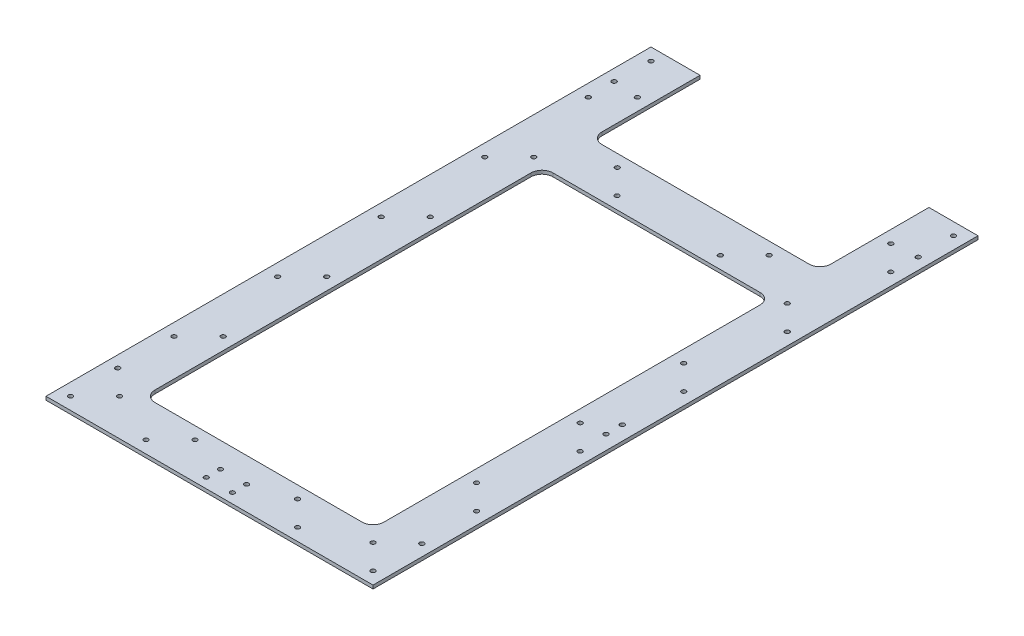
SolidWorks part; units mm, degrees
ref_plane "Front Plane" through (0, 0, 0) normal (0, 0, 1) x (1, 0, 0)
ref_plane "Top Plane" through (0, 0, 0) normal (0, 1, 0) x (1, 0, 0)
ref_plane "Right Plane" through (0, 0, 0) normal (1, 0, 0) x (0, 0, -1)
sketch "Sketch1" plane through (0, 0, 0) normal (0, 1, 0) x (1, 0, 0)
  line L1 (150, -300) -> (-150, -300)
  line L2 (150, -300) -> (150, 300)
  line L3 (150, 300) -> (-150, 300)
  line L4 (-150, -300) -> (-150, 300)
  line L5 (150, -300) -> (-150, 300) construction
  line L6 (150, 300) -> (-150, -300) construction
  point P0 (0, 0)
  dimension "D1" = 600
  dimension "D2" = 300
extrude "Boss-Extrude1" add sketch "Sketch1" along normal blind 3.175
sketch "Sketch3" plane through (0, 3.175, 0) normal (0, 1, 0) x (1, 0, 0)
  line L0 (-95, -255) -> (95, -255)
  line L1 (0, 255) -> (0, -300) construction
  line L2 (105, -245) -> (105, 100)
  line L3 (95, 110) -> (-95, 110)
  line L4 (105, 255) -> (105, 165)
  line L5 (150, 300) -> (-150, 300) construction
  line L6 (95, 155) -> (-95, 155)
  line L8 (0, -300) -> (0, -342.0806) construction
  line L9 (-105, 255) -> (-105, 165)
  line L10 (-105, -245) -> (-105, 100)
  line L11 (50.6601, -255) -> (50.6601, -300) construction
  line L12 (-150, -300) -> (150, -300) construction
  line L13 (105, 27.7939) -> (150, 27.7939) construction
  line L14 (150, -300) -> (150, 300) construction
  line L15 (-150, 27.7939) -> (-105, 27.7939) construction
  line L16 (-150, 300) -> (-150, -300) construction
  line L17 (54.6047, 155) -> (54.6047, 110) construction
  line L18 (105, 255) -> (150, 255)
  line L19 (150, 255) -> (150, 300)
  line L20 (150, 300) -> (-150, 300)
  line L21 (-150, 300) -> (-150, 255)
  line L22 (-150, 255) -> (-105, 255)
  arc A1 (-105, 165) -> (-95, 155) centre (-95, 165) ccw
  arc A3 (105, 165) -> (95, 155) centre (95, 165) cw
  arc A4 (105, 100) -> (95, 110) centre (95, 100) ccw
  arc A5 (-105, 100) -> (-95, 110) centre (-95, 100) cw
  arc A6 (-105, -245) -> (-95, -255) centre (-95, -245) ccw
  arc A7 (95, -255) -> (105, -245) centre (95, -245) ccw
  point P17 (0, 300)
  point P18 (0, 155)
  point P19 (0, 110)
  point P20 (0, -255)
  point P22 (-105.4457, 300)
  point P25 (-105, 155)
  point P28 (105.4457, 300)
  point P31 (105, 155)
  point P34 (105, 110)
  point P37 (-105, 110)
  point P40 (-105, -255)
  point P43 (105, -255)
  dimension "D1" = 45
  dimension "D4" = 10
  dimension "D2" = 45
  dimension "D3" = 145
extrude "Cut-Extrude1" cut sketch "Sketch3" against normal blind 10
sketch "Sketch4" plane through (0, 3.175, 0) normal (0, 1, 0) x (1, 0, 0)
  line L0 (-150, -300) -> (150, -300) construction
  circle A0 centre (12, -291) radius 2.05
  circle A1 centre (-12, -291) radius 2.05
  circle A2 centre (-12, -278) radius 2.05
  circle A3 centre (12, -278) radius 2.05
  point P2 (-27.0179, -300)
  point P16 (-27, -300)
  dimension "D1" = 4.1
  dimension "D2" = 15
  dimension "D3" = 39
  dimension "D4" = 9
  dimension "D5" = 22
extrude "Cut-Extrude2" cut sketch "Sketch4" against normal blind 51
sketch "Sketch5" plane through (0, 3.175, 0) normal (0, 1, 0) x (1, 0, 0)
  circle A0 centre (137, -73.2648) radius 2.1
  circle A1 centre (137, -58.2648) radius 2.1
  circle A2 centre (132, -58.2648) radius 2.15 construction
  point P6 (0, 0)
  point P7 (0, 0)
  point P8 (137.7511, -58.2648)
  point P9 (137.7511, -73.2648)
  point P10 (0, 0)
  dimension "D1" = 4.2
  dimension "D2" = 5
extrude "Cut-Extrude3" cut sketch "Sketch5" against normal blind 67
sketch "Sketch7" plane through (0, 3.175, 0) normal (0, 1, 0) x (1, 0, 0)
  line L0 (138.75, -300) -> (138.75, 255) construction
  line L1 (116.25, -300) -> (116.25, 255) construction
  line L2 (150, -187.519) -> (138.75, -187.519) construction
  line L3 (150, -300) -> (150, 255) construction
  line L4 (138.75, -187.519) -> (127.5, -187.519) construction
  line L5 (127.5, -187.519) -> (116.25, -187.519) construction
  line L6 (116.25, -187.519) -> (105, -187.519) construction
  line L7 (105, -245) -> (105, 100) construction
  line L8 (-150, -300) -> (150, -300) construction
  line L10 (150, 121.25) -> (0, 121.25) construction
  line L11 (105, 255) -> (150, 255) construction
  line L12 (150, 143.75) -> (0, 143.75) construction
  line L13 (33.148, 155) -> (33.148, 143.75) construction
  line L14 (-95, 155) -> (95, 155) construction
  line L15 (33.148, 143.75) -> (33.148, 132.5) construction
  line L16 (33.148, 132.5) -> (33.148, 121.25) construction
  line L17 (33.148, 121.25) -> (33.148, 110) construction
  line L18 (95, 110) -> (-95, 110) construction
  line L19 (150, -288.75) -> (0, -288.75) construction
  line L20 (150, -266.25) -> (0, -266.25) construction
  line L21 (55.7313, -255) -> (55.7313, -266.25) construction
  line L22 (-95, -255) -> (95, -255) construction
  line L23 (55.7313, -266.25) -> (55.7313, -277.5) construction
  line L24 (55.7313, -277.5) -> (55.7313, -288.75) construction
  line L25 (55.7313, -288.75) -> (55.7313, -300) construction
  line L26 (-42.5408, 110) -> (-42.5408, -255) construction
  line L27 (0, -288.75) -> (0, -389.9124) construction
  line L29 (-150, 255) -> (-105, 255) construction
  circle A0 centre (138.75, -288.75) radius 2.05
  circle A1 centre (116.25, -266.25) radius 2.05
  circle A2 centre (47.0236, -266.25) radius 2.05
  circle A3 centre (69.5236, -288.75) radius 2.05
  circle A4 centre (116.25, -171.25) radius 2.05
  circle A5 centre (138.75, -193.75) radius 2.05
  circle A6 centre (116.25, -76.25) radius 2.05
  circle A7 centre (138.75, -98.75) radius 2.05
  circle A8 centre (116.25, 18.75) radius 2.05
  circle A9 centre (138.75, -3.75) radius 2.05
  circle A10 centre (116.25, 113.75) radius 2.05
  circle A11 centre (138.75, 91.25) radius 2.05
  circle A12 centre (116.25, 208.75) radius 2.05
  circle A13 centre (138.75, 186.25) radius 2.05
  circle A16 centre (47.3578, 121.25) radius 2.05
  circle A17 centre (69.635, 143.75) radius 2.05
  circle A18 centre (-47.3578, 121.25) radius 2.05
  circle A19 centre (-69.635, 143.75) radius 2.05
  circle A21 centre (-116.25, 208.75) radius 2.05
  circle A22 centre (-138.75, 186.25) radius 2.05
  circle A23 centre (-138.75, 91.25) radius 2.05
  circle A24 centre (-116.25, 18.75) radius 2.05
  circle A25 centre (-116.25, 113.75) radius 2.05
  circle A26 centre (-116.25, -76.25) radius 2.05
  circle A27 centre (-138.75, -3.75) radius 2.05
  circle A28 centre (-138.75, -98.75) radius 2.05
  circle A29 centre (-116.25, -171.25) radius 2.05
  circle A30 centre (-138.75, -193.75) radius 2.05
  circle A31 centre (-116.25, -266.25) radius 2.05
  circle A32 centre (-138.75, -288.75) radius 2.05
  circle A33 centre (-47.0236, -266.25) radius 2.05
  circle A34 centre (-69.5236, -288.75) radius 2.05
  circle A35 centre (116.25, 303.75) radius 2.05 [skipped]
  circle A36 centre (138.75, 281.25) radius 2.05 [skipped]
  circle A37 centre (-138.75, 243.75) radius 2.05
  circle A38 centre (138.75, 243.75) radius 2.05
  dimension "D1" = 4.1
  dimension "D2" = 4.1
  dimension "D6" = 4.1
  dimension "D5" = 95
  dimension "D7" = 11.25
  dimension "D3" = 2
  dimension "D4" = 7
extrude "Cut-Extrude4" cut sketch "Sketch7" against normal blind 10
sketch "Sketch8" plane through (0, 3.175, 0) normal (0, 1, 0) x (1, 0, 0)
  line L0 (150, -300) -> (150, 255) construction
  circle A0 centre (139.5, 210.666) radius 2.1
  circle A1 centre (139.5, -244.7019) radius 2.1
  point P6 (0, 0)
  point P7 (139.2533, -244.7019)
  point P10 (0, 0)
  point P11 (0, 0)
  dimension "D1" = 4.2
  dimension "D2" = 10.5
extrude "Cut-Extrude5" cut sketch "Sketch8" against normal blind 10
ref_plane "Plane1" through (0, 0, 0) normal (1, 0, 0) x (0, 0, -1)
mirror "Mirror1" about plane through (0, 0, 0) normal (1, 0, 0) of "Cut-Extrude5"
equation "\"D2@Sketch7\"=\"D1@Sketch7\""
